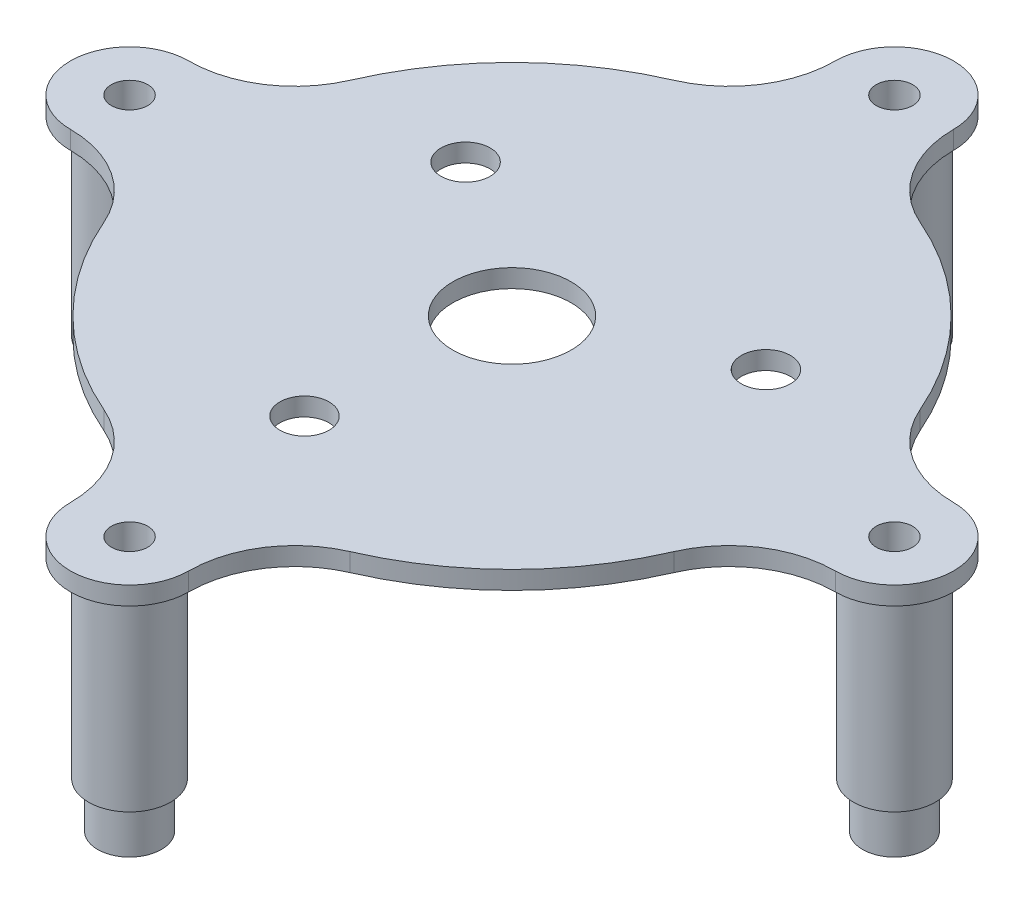
SolidWorks part; units mm, degrees
ref_plane "Front Plane" through (0, 0, 0) normal (0, 0, 1) x (1, 0, 0)
ref_plane "Top Plane" through (0, 0, 0) normal (0, 1, 0) x (1, 0, 0)
ref_plane "Right Plane" through (0, 0, 0) normal (1, 0, 0) x (0, 0, -1)
sketch "Sketch1" plane through (0, 0, 0) normal (0, 1, 0) x (1, 0, 0)
  line L0 (0, 0) -> (110.375, 0) construction
  circle A0 centre (42, 0) radius 2
  circle A1 centre (42, 0) radius 4.5
  circle A2 centre (42, 0) radius 3.5
  circle A3 centre (0, -42) radius 4.5
  circle A4 centre (0, -42) radius 3.5
  circle A5 centre (0, -42) radius 2
  circle A6 centre (-42, 0) radius 4.5
  circle A7 centre (-42, 0) radius 3.5
  circle A8 centre (-42, 0) radius 2
  circle A9 centre (0, 42) radius 4.5
  circle A10 centre (0, 42) radius 3.5
  circle A11 centre (0, 42) radius 2
  circle A12 centre (42, 0) radius 6.5
  arc A13 (31.3005, 13.5311) -> (42, 6.5) centre (42, 18.1565) ccw
  arc A14 (31.3005, -13.5311) -> (42, -6.5) centre (42, -18.1565) cw
  arc A15 (13.5311, -31.3005) -> (6.5, -42) centre (18.1565, -42) ccw
  arc A16 (-13.5311, -31.3005) -> (-6.5, -42) centre (-18.1565, -42) cw
  circle A17 centre (0, -42) radius 6.5
  arc A18 (-31.3005, -13.5311) -> (-42, -6.5) centre (-42, -18.1565) ccw
  arc A19 (-31.3005, 13.5311) -> (-42, 6.5) centre (-42, 18.1565) cw
  circle A20 centre (-42, 0) radius 6.5
  arc A21 (-13.5311, 31.3005) -> (-6.5, 42) centre (-18.1565, 42) ccw
  arc A22 (13.5311, 31.3005) -> (6.5, 42) centre (18.1565, 42) cw
  circle A23 centre (0, 42) radius 6.5
  point P20 (0, 0)
  circle B0 centre (0, 0) radius 34.1
  circle B1 centre (-17.1777, 12.08) radius 2.7
  circle B2 centre (19.0504, 8.8364) radius 2.7
  circle B3 centre (-1.8727, -20.9163) radius 2.7
  circle B4 centre (0, 0) radius 6.5
  dimension "D1" = 4
  dimension "D2" = 7
  dimension "D3" = 9
  dimension "D6" = 13
  dimension "D4" = 42
  dimension "D5" = 4
sketch_block_instance "Block1-1"
sketch_block "Block1"
extrude "Boss-Extrude1" add sketch "Sketch1" along normal blind 2 contours B4 B0 B3 B2 B1 | B0 A19 A20 A18 | A20 A6 | A6 A7 | A7 A8 | B0 A22 A23 A21 | A23 A9 | A9 A10 | A10 A11 | L0 B0 A14 A12 | B0 L0 A12 A13 | A12 L0 A1 | L0 A12 A1 | L0 A1 A2 | A1 L0 A2 | A2 L0 A0 | L0 A2 A0 | B0 A16 A17 A15 | A17 A3 | A3 A4 | A4 A5 region at (32.4483, 0, 6.7134) region at (35.4462, 0, -5.6875) region at (35.4462, 0, 5.6875) region at (37.5066, 0, -4.4934) region at (36.5, 0, 0.1453) region at (42, 0, -4.3994) region at (38, 0, 0.1006) region at (0, 0, -35.4462) region at (0, 0, 35.4462) region at (42, 0, -3.4217) region at (39.25, 0, 0.0783) region at (0, 0, -35.6838) region at (0, 0, 48.3162) region at (-35.4462, 0, 0) region at (-37.5338, 0, -4.4662) region at (-4.3727, 0, 42) region at (-3.401, 0, 42) region at (-46.3727, 0, 0) region at (-45.401, 0, 0) region at (-4.3727, 0, -42) region at (-3.401, 0, -42)
extrude "Boss-Extrude2" add sketch "Sketch1<3>" against normal blind 26 contours L0 A1 A2 | L0 A2 A0 | A2 L0 A0 | A1 L0 A2 | A3 A4 | A4 A5 | A6 A7 | A7 A8 | A9 A10 | A10 A11 region at (42, 0, -4.3994) region at (38, 0, 0.1006) region at (42, 0, -3.4217) region at (39.25, 0, 0.0783) region at (-4.3727, 0, 42) region at (-3.401, 0, 42) region at (-46.3727, 0, 0) region at (-45.401, 0, 0) region at (-4.3727, 0, -42) region at (-3.401, 0, -42)
sketch "Sketch1<3>" plane through (0, 0, 0) normal (0, 1, 0) x (1, 0, 0) same geometry as "Sketch1"
extrude "Cut-Extrude1" cut sketch "Sketch1<4>" along normal blind 5 from surface contours A3 A4 | A1 L0 A2 | L0 A1 A2 | A9 A10 | A6 A7 region at (42, 0, -4.3994) region at (38, 0, 0.1006) region at (-4.3727, 0, 42) region at (-46.3727, 0, 0) region at (-4.3727, 0, -42) starting at face at (0, -26, 46.5)
sketch "Sketch1<4>" plane through (0, 0, 0) normal (0, 1, 0) x (1, 0, 0) same geometry as "Sketch1"
